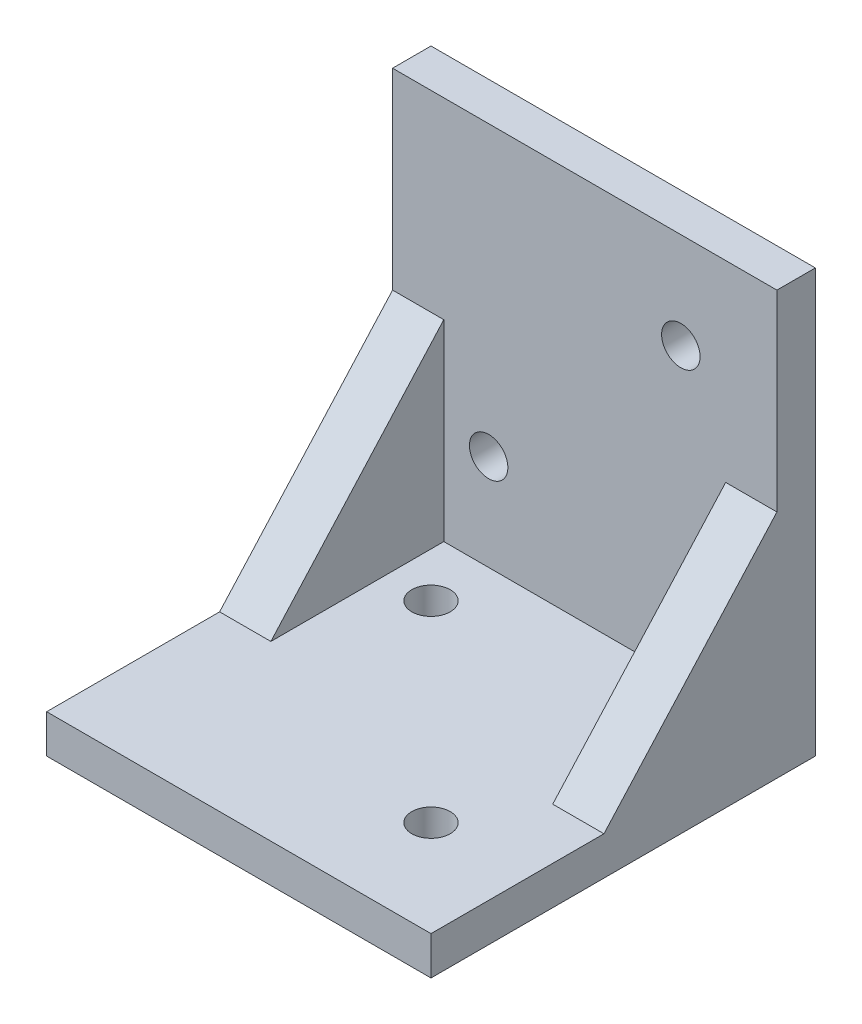
SolidWorks part; units mm, degrees
ref_plane "Front Plane" through (0, 0, 0) normal (0, 0, 1) x (1, 0, 0)
ref_plane "Top Plane" through (0, 0, 0) normal (0, 1, 0) x (1, 0, 0)
ref_plane "Right Plane" through (0, 0, 0) normal (1, 0, 0) x (0, 0, -1)
sketch "Sketch1" plane through (0, 0, 0) normal (0, 1, 0) x (1, 0, 0)
  line L0 (0, 0) -> (-15, 15) construction
  line L1 (-15, -15) -> (15, -15)
  line L2 (-15, -15) -> (-15, 15)
  line L3 (-15, 15) -> (15, 15)
  line L4 (15, -15) -> (15, 15)
  line L5 (-15, -15) -> (15, 15) construction
  line L7 (0, 0) -> (15, -15) construction
  circle A0 centre (-7.5, 7.5) radius 1.5
  circle A2 centre (7.5, -7.5) radius 1.5
  point P0 (0, 0)
  point P9 (0, 0)
  point P10 (14.9609, -12.7856)
  point P12 (21.9645, -19.65)
  point P13 (0, 0)
  point P14 (21.2911, -16.9566)
  point P15 (0, 0)
  point P16 (5.9882, -6.3111)
  point P17 (0.8189, -10.5591)
  point P18 (0, 0)
  dimension "D3" = 3
  dimension "D4" = 3
  dimension "D1" = 30
  dimension "D2" = 30
extrude "Boss-Extrude1" add sketch "Sketch1" along normal blind 3
sketch "Sketch2" plane through (0, 3, 0) normal (0, 1, 0) x (1, 0, 0)
  line L0 (15, -15) -> (15, 15) construction
  line L1 (-15, 15) -> (15, 15)
  line L2 (-15, 15) -> (-15, 12)
  line L3 (-15, 12) -> (15, 12)
  line L4 (15, 15) -> (15, 12)
  point P5 (0, 0)
  dimension "D1" = 3
extrude "Boss-Extrude2" add sketch "Sketch2" along normal blind 30
sketch "Sketch3" plane through (0, 0, -15) normal (0, 0, -1) x (-1, 0, 0)
  line L0 (-15, 3) -> (15, 3) construction
  line L1 (-15, 33) -> (-15, 0) construction
  line L2 (15, 33) -> (15, 0) construction
  line L3 (16.5, 0) -> (-16.5, 0) construction
  line L4 (-15, 33) -> (0, 18) construction
  line L5 (0, 16.5) -> (0, -16.5) construction
  line L6 (0, 18) -> (15, 3) construction
  line L7 (15, 33) -> (0, 18) construction
  line L8 (0, 18) -> (-15, 3) construction
  circle A0 centre (-7.5, 25.5) radius 1.5
  circle A1 centre (7.5, 10.5) radius 1.5
  dimension "D2" = 3
  dimension "D3" = 3
  dimension "D1" = 3
extrude "Cut-Extrude1" cut sketch "Sketch3" against normal blind 30
sketch "Sketch4" plane through (-15, 0, 0) normal (-1, 0, 0) x (0, 0, 1)
  line L0 (-12, 18) -> (1.5, 3)
  line L1 (-12, 33) -> (-12, 3) construction
  line L2 (-12, 3) -> (15, 3) construction
  line L3 (1.5, 3) -> (-12, 3)
  line L4 (-12, 3) -> (-12, 18)
extrude "Boss-Extrude3" add sketch "Sketch4" against normal blind 4
extrude "Boss-Extrude4" add sketch "Sketch4<2>" along normal blind 4 from surface starting at face at (15, 12, -4)
sketch "Sketch4<2>" plane through (-15, 0, 0) normal (-1, 0, 0) x (0, 0, 1) same geometry as "Sketch4"
